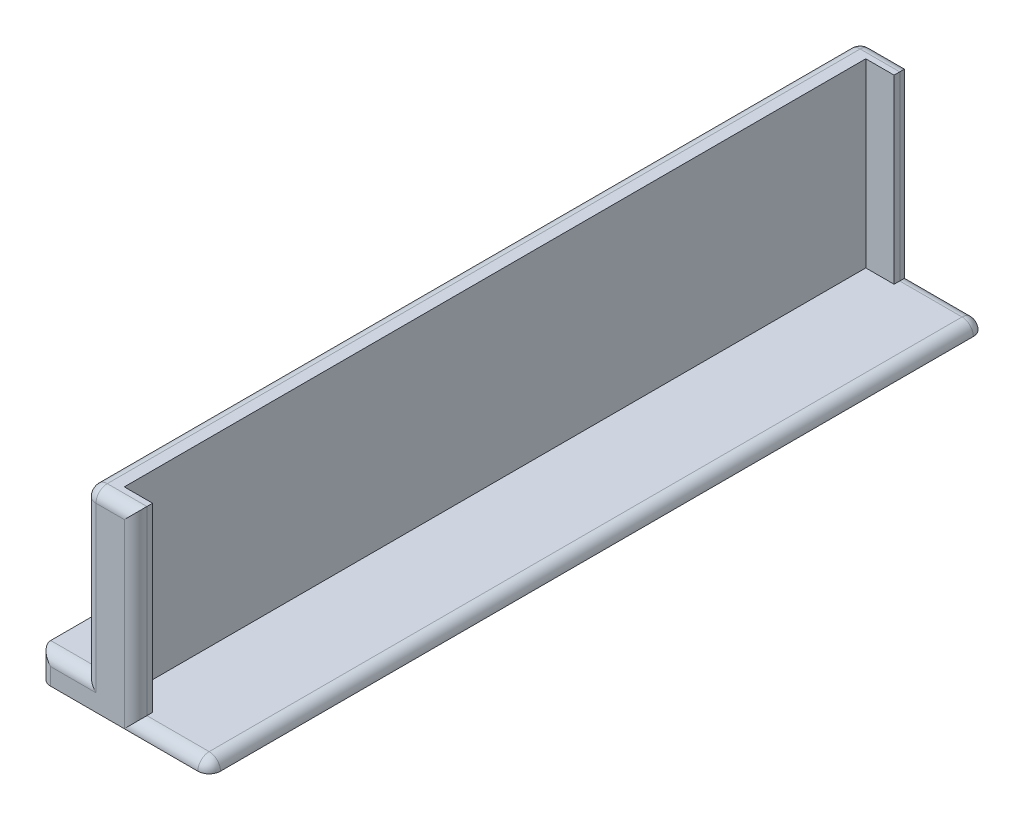
SolidWorks part; units mm, degrees
ref_plane "Plan de face" through (0, 0, 0) normal (0, 0, 1) x (1, 0, 0)
ref_plane "Plan de dessus" through (0, 0, 0) normal (0, 1, 0) x (1, 0, 0)
ref_plane "Plan de droite" through (0, 0, 0) normal (1, 0, 0) x (0, 0, -1)
sketch "Esquisse1" plane through (0, 0, 0) normal (0, 0, 1) x (1, 0, 0)
  line L0 (0, 0) -> (30, 0)
  line L5 (0, 0) -> (30, 0) construction
  line L6 (0, 0) -> (0, 34) construction
  line L7 (0, 34) -> (30, 34) construction
  line L8 (30, 0) -> (30, 34) construction
  line L9 (30, 0) -> (30, 2)
  line L10 (30, 2) -> (12, 2)
  line L11 (12, 2) -> (12, 34)
  line L12 (12, 34) -> (8, 34)
  line L13 (8, 34) -> (8, 5)
  line L14 (8, 5) -> (0, 5)
  line L15 (0, 5) -> (0, 0)
  dimension "D1" = 34
  dimension "D2" = 30
  dimension "D3" = 2
  dimension "D4" = 5
  dimension "D5" = 18
  dimension "D6" = 4
extrude "Boss.-Extru.1" add sketch "Esquisse1" along normal blind 131
sketch "Esquisse2" plane through (0, 5, 0) normal (0, 1, 0) x (1, 0, 0)
  line L0 (8, 0) -> (0, 0) construction
  line L1 (8, -131) -> (0, -131) construction
  line L2 (0, -131) -> (0, 0) construction
  circle A0 centre (4, -20) radius 1.5
  circle A1 centre (4, -111) radius 1.5
  dimension "D4" = 3
  dimension "D6" = 3
  dimension "D1" = 20
  dimension "D2" = 20
  dimension "D3" = 4
  dimension "D5" = 4
extrude "Enlèv. mat.-Extru.1" cut sketch "Esquisse2" against normal up to surface (5 mm away) up to face at (15, 0, 65.5)
hole_wizard "Fraisage pour vis à tête fraisée M31" positions "Esquisse3" profile "Esquisse4" countersink size "M3" standard "ISO" end condition up to next
sketch "Esquisse3" plane through (0, 5, 0) normal (0, 1, 0) x (1, 0, 0)
  point P0 (4, -111)
  point P3 (4, -20)
sketch "Esquisse4" plane through (4, 5, 111) normal (1, 0, 0) x (0, 0, 1)
  line L0 (0, 0) -> (0, 5)
  line L1 (0, 5) -> (1.7, 5)
  line L2 (1.7, 5) -> (1.7, 1.45)
  line L3 (1.7, 1.45) -> (3.15, 0)
  line L5 (3.15, 0) -> (0, 0)
  line L6 (-1.7, 1.45) -> (-3.15, 0) construction
  line L11 (0, -6.35) -> (0, 107.95) construction
  dimension "Diamètre du perçage jusqu'au prochain" = 3.4
  dimension "Profondeur du perçage jusqu'au prochain" = 5
  dimension "Diamètre du fraisage entrant" = 6.3
  dimension "Angle du fraisage entrant" = 90
sketch "Esquisse5" plane through (0, 0, 131) normal (0, 0, 1) x (1, 0, 0)
  line L0 (8, 34) -> (17, 34)
  line L1 (17, 34) -> (17, 2)
  line L2 (30, 2) -> (12, 2) construction
  line L3 (17, 2) -> (30, 2)
  line L4 (12, 2) -> (12, 34) construction
  line L8 (0, 5) -> (0, 0)
  line L9 (0, 0) -> (30, 0)
  line L10 (30, 0) -> (30, 2)
  line L11 (30, 2) -> (12, 2)
  line L12 (12, 2) -> (12, 34)
  line L13 (12, 34) -> (8, 34)
  line L14 (8, 34) -> (8, 5)
  line L15 (8, 5) -> (0, 5)
  line L16 (0, 5) -> (0, 0)
  line L17 (0, 0) -> (30, 0)
  line L18 (30, 0) -> (30, 2)
  line L22 (8, 34) -> (8, 5)
  line L23 (8, 5) -> (0, 5)
  dimension "D2" = 5
  dimension "D1" = 0
extrude "Boss.-Extru.2" add sketch "Esquisse5" along normal blind 3
sketch "Esquisse6" plane through (0, 0, 0) normal (0, 0, -1) x (-1, 0, 0)
  line L0 (-8, 34) -> (-17, 34)
  line L1 (-17, 34) -> (-17, 2)
  line L2 (-30, 2) -> (-12, 2) construction
  line L3 (-17, 2) -> (-30, 2)
  line L4 (-12, 2) -> (-12, 34) construction
  line L8 (0, 0) -> (0, 5)
  line L9 (0, 5) -> (-8, 5)
  line L10 (-8, 5) -> (-8, 34)
  line L11 (-8, 34) -> (-12, 34)
  line L12 (-12, 34) -> (-12, 2)
  line L13 (-12, 2) -> (-30, 2)
  line L14 (-30, 2) -> (-30, 0)
  line L15 (-30, 0) -> (0, 0)
  line L16 (0, 0) -> (0, 5)
  line L17 (0, 5) -> (-8, 5)
  line L18 (-8, 5) -> (-8, 34)
  line L22 (-30, 2) -> (-30, 0)
  line L23 (-30, 0) -> (0, 0)
  dimension "D2" = 5
  dimension "D1" = 0
extrude "Boss.-Extru.3" add sketch "Esquisse6" along normal blind 3
fillet "Congé3" [suppressed] radius 2 type face fillet
fillet "Congé5" radius 2 16 edges at (17, 18, -3) (8, 19.5, -3) (8, 34, 65.5) (8, 19.5, 134) (17, 18, 134) (12.5, 34, -3) (12.5, 34, 134) (4, 5, -3) (23.5, 2, -3) (0, 2.5, -3) (0, 2.5, 134) (4, 5, 134) (23.5, 2, 134) (30, 1, -3) (30, 1, 134) (30, 2, 65.5)
